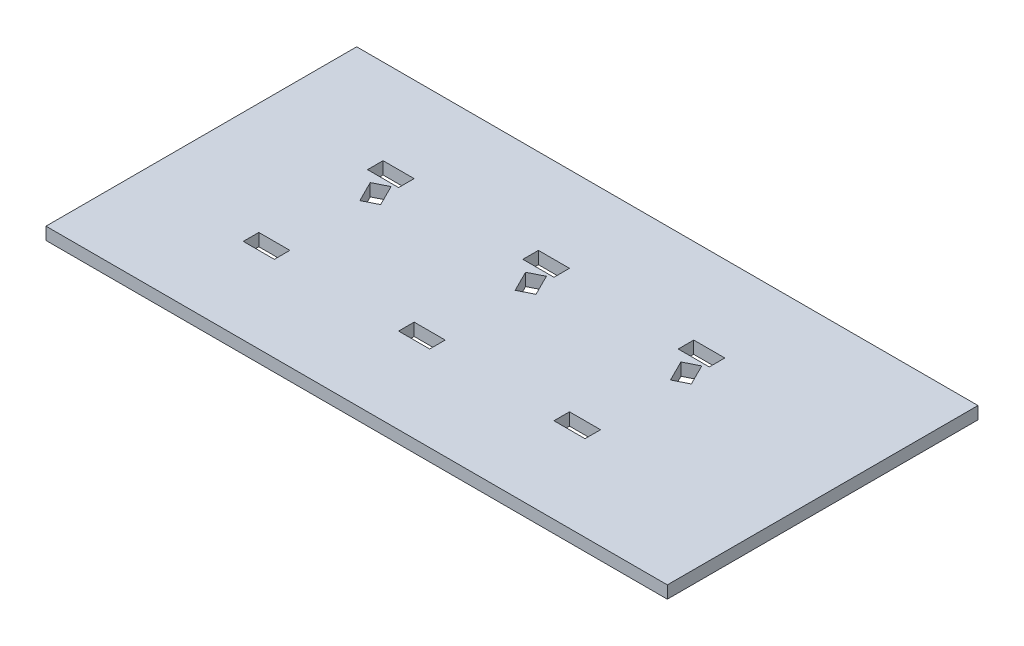
SolidWorks part; units mm, degrees
ref_plane "Front Plane" through (0, 0, 0) normal (0, 0, 1) x (1, 0, 0)
ref_plane "Top Plane" through (0, 0, 0) normal (0, 1, 0) x (1, 0, 0)
ref_plane "Right Plane" through (0, 0, 0) normal (1, 0, 0) x (0, 0, -1)
sketch "Sketch1" plane through (0, 0, 0) normal (0, 1, 0) x (1, 0, 0)
  line L1 (-50.8, -25.4) -> (50.8, -25.4)
  line L2 (-50.8, -25.4) -> (-50.8, 25.4)
  line L3 (-50.8, 25.4) -> (50.8, 25.4)
  line L4 (50.8, -25.4) -> (50.8, 25.4)
  line L5 (0, 25.4) -> (0, -25.4) construction
  line L6 (-50.8, 0) -> (50.8, 0) construction
  point P0 (0, 0)
  dimension "D1" = 50.8
  dimension "D2" = 101.6
extrude "Boss-Extrude1" add sketch "Sketch1" along normal blind 2.032
sketch "Sketch2" plane through (0, 2.032, 0) normal (0, 1, 0) x (1, 0, 0)
  line L0 (-3.3577, 3.8746) -> (-1.0859, 5.0107)
  line L1 (-3.3577, 3.8746) -> (-5.0618, 7.2822)
  line L2 (-1.0859, 5.0107) -> (-2.7901, 8.4183)
  line L3 (-5.0618, 7.2822) -> (-2.7901, 8.4183)
  line L5 (-1.1176, 0) -> (1.1176, 0) construction
  circle A0 centre (0, 0) radius 5.127 construction
  dimension "D1" = 10.254
  dimension "D3" = 3.81
  dimension "D4" = 2.54
  dimension "D2" = 63.43
extrude "Cut-Extrude1" cut sketch "Sketch2" against normal through all contours L3 L1 L0 L2 region at (-3.0739, 2.032, -6.1464)
sketch "Sketch3" plane through (0, 2.032, 0) normal (0, 1, 0) x (1, 0, 0)
  line L0 (-7.112, 8.89) -> (-2.032, 8.89)
  line L1 (-7.112, 8.89) -> (-7.112, 11.43)
  line L2 (-2.032, 8.89) -> (-2.032, 11.43)
  line L3 (-7.112, 11.43) -> (-2.032, 11.43)
  line L4 (-1.1176, 0) -> (1.1176, 0) construction
  line L5 (0, -1.1176) -> (0, 1.1176) construction
  dimension "D1" = 2.54
  dimension "D2" = 5.08
  dimension "D3" = 2.032
  dimension "D4" = 8.89
extrude "Cut-Extrude2" cut sketch "Sketch3" against normal through all
mirror "Mirror1" about plane through (0, 0, 0) normal (0, 0, 1) of "Cut-Extrude2"
pattern_linear "LPattern1" count 2 spacing 25.4 along (-1, 0, 0) count 2 spacing 25.4 along (1, 0, 0) of "Cut-Extrude1", "Cut-Extrude2", "Mirror1"
equation "\"Arrow Height\"= 1in"
equation "\"Button Height\"= 2in"
equation "\"Button Width\"= 4in"
equation "\"Haptic Diameter\"= 10mm"
equation "\"Haptic Thickness\"= 2.7mm"
equation "\"D1@Sketch1\"=\"Button Height\""
equation "\"D2@Sketch1\"=\"Button Width\""
equation "\"D1@Sketch2\"=\"Haptic Diameter\"+.01in"
equation "\"Arrow Spacing\"= 1in"
equation "\"Arrow Width\" = 0.75in"
equation "\"Haptic Wire Angle\" = 63.43"
equation "\"Haptic Wire Width\" = .1in"
equation "\"Hatic Wire Height\" = .15in"
equation "\"D2@Sketch2\"=\"Haptic Wire Angle\""
equation "\"D4@Sketch2\"=\"Haptic Wire Width\""
equation "\"D3@Sketch2\"=\"Hatic Wire Height\""
